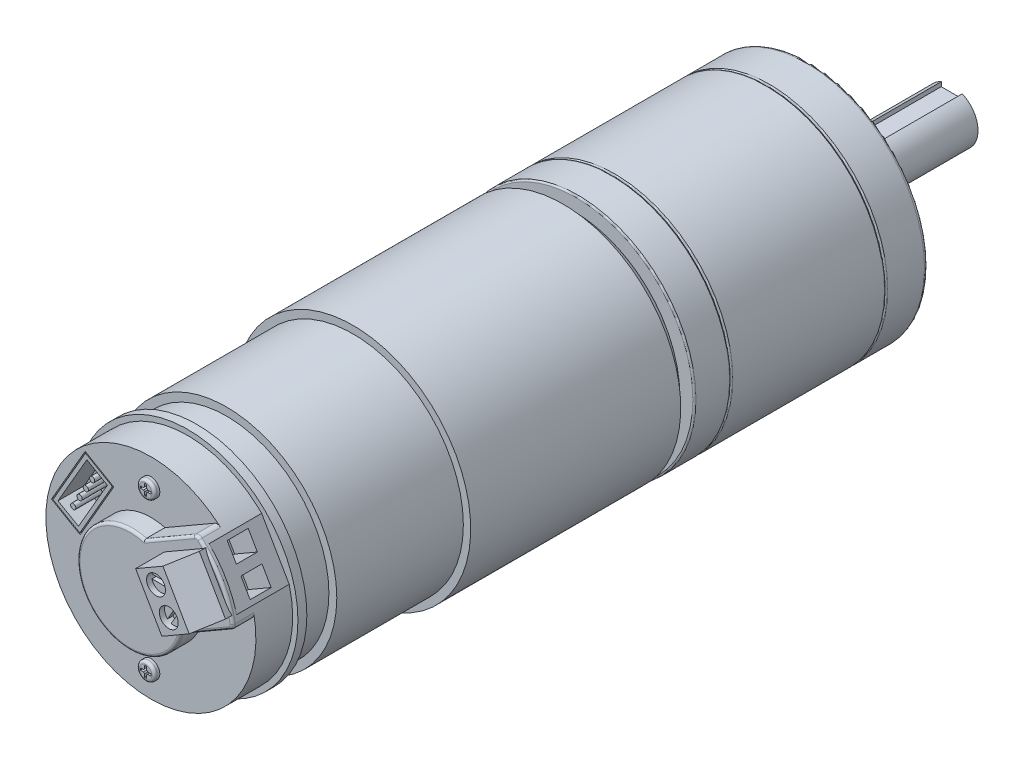
SolidWorks part; units mm, degrees
ref_plane "Front Plane" through (0, 0, 0) normal (0, 0, 1) x (1, 0, 0)
ref_plane "Top Plane" through (0, 0, 0) normal (0, 1, 0) x (1, 0, 0)
ref_plane "Right Plane" through (0, 0, 0) normal (1, 0, 0) x (0, 0, -1)
sketch "Sketch1" plane through (0, 0, 0) normal (0, 0, 1) x (1, 0, 0)
  circle A0 centre (-32.232, 14.9868) radius 22.5
extrude "Boss-Extrude1" add sketch "Sketch1" along normal blind 8
fillet "Fillet1" radius 0.3 1 edges at (-9.732, 14.9868, 8)
sketch "Sketch2" plane through (0, 0, 8) normal (0, 0, 1) x (1, 0, 0)
  circle A0 centre (-32.232, 14.9868) radius 22.5
extrude "Boss-Extrude2" add sketch "Sketch2" along normal blind 29.5
fillet "Fillet3" radius 0.3 1 edges at (-9.732, 14.9868, 37.5)
sketch "Sketch3" plane through (0, 0, 37.5) normal (0, 0, 1) x (1, 0, 0)
  circle A0 centre (-32.232, 14.9868) radius 22.5
extrude "Boss-Extrude5" add sketch "Sketch3" along normal blind 7
fillet "Fillet4" radius 0.3 3 edges at (-9.732, 14.9868, 8) (-9.732, 14.9868, 37.5) (-9.732, 14.9868, 44.5)
sketch "Sketch4" plane through (0, 0, 44.5) normal (0, 0, 1) x (1, 0, 0)
  circle A0 centre (-32.232, 14.9868) radius 5
extrude "Boss-Extrude7" add sketch "Sketch4" along normal blind 0.1
sketch "Sketch5" plane through (0, 0, 44.6) normal (0, 0, 1) x (1, 0, 0)
  circle A0 centre (-32.232, 14.9868) radius 21
extrude "Boss-Extrude8" add sketch "Sketch5" along normal blind 66.5
fillet "Fillet6" radius 2 1 edges at (-11.232, 14.9868, 44.6)
ref_plane "Plane1" through (0, 0, 47) normal (0, 0, 1) x (1, 0, 0)
sketch "Sketch6" plane through (0, 0, 47) normal (0, 0, 1) x (1, 0, 0)
  line L2 (-28.132, -5.609) -> (-28.132, -7.0347)
  line L4 (-36.332, -5.609) -> (-36.332, -7.0347)
  arc A0 (-28.132, -7.0347) -> (-36.332, -7.0347) centre (-32.232, 14.9868) ccw
  arc A1 (-28.132, -5.609) -> (-36.332, -5.609) centre (-32.232, 14.9868) ccw
  point P4 (-32.232, -6.0132)
extrude "Boss-Extrude9" add sketch "Sketch6" along normal blind 40
sketch "Sketch7" plane through (0, 0, 111.1) normal (0, 0, 1) x (1, 0, 0)
  circle A0 centre (-32.232, 14.9868) radius 19.5
extrude "Boss-Extrude10" add sketch "Sketch7" along normal blind 5.7
sketch "Sketch8" plane through (0, 0, 116.8) normal (0, 0, 1) x (1, 0, 0)
  circle A0 centre (-32.232, 14.9868) radius 21
extrude "Boss-Extrude11" add sketch "Sketch8" along normal blind 1.7
sketch "Sketch9" plane through (0, 0, 118.5) normal (0, 0, 1) x (1, 0, 0)
  circle A0 centre (-32.232, 14.9868) radius 20
extrude "Boss-Extrude12" add sketch "Sketch9" along normal blind 7
fillet "Fillet7" radius 0.7 1 edges at (-9.732, 14.9868, 0)
sketch "Sketch21" plane through (0, 0, 125.5) normal (0, 0, 1) x (1, 0, 0)
  line L0 (-45.6944, 15.3693) -> (-51.1503, 18.5193)
  line L2 (-39.2944, 26.4544) -> (-44.7503, 29.6044)
  line L3 (-44.7503, 29.6044) -> (-51.1503, 18.5193)
  line L4 (-39.2944, 26.4544) -> (-45.6944, 15.3693)
  point P6 (-42.4944, 20.9118)
extrude "Cut-Extrude5" cut sketch "Sketch21" against normal blind 5
sketch "Sketch22" plane through (0, 0, 120.5) normal (0, 0, 1) x (1, 0, 0)
  line L0 (-44.4209, 28.375) -> (-49.9209, 18.8487)
  line L1 (-49.9209, 18.8487) -> (-46.0238, 16.5987)
  line L2 (-46.0238, 16.5987) -> (-40.5238, 26.125)
  line L3 (-40.5238, 26.125) -> (-44.4209, 28.375)
  line L4 (-39.5676, 26.3812) -> (-44.6771, 29.3312)
  line L5 (-44.6771, 29.3312) -> (-50.8771, 18.5925)
  line L6 (-50.8771, 18.5925) -> (-45.7676, 15.6425)
  line L7 (-45.7676, 15.6425) -> (-39.5676, 26.3812)
  circle A0 centre (-45.8223, 21.4476) radius 0.5
  circle A1 centre (-47.0223, 19.3691) radius 0.5
  circle A2 centre (-43.4223, 25.6045) radius 0.5
  circle A3 centre (-44.6223, 23.5261) radius 0.5
extrude "Boss-Extrude20" add sketch "Sketch22" along normal blind 5 contours L6 L7 L4 L5 L3 L2 L1 L0 | A2 | A3 | A0 | A1 region at (-42.8213, 21.1006, 120.5) region at (-45.8223, 21.4476, 120.5) region at (-47.0223, 19.3691, 120.5) region at (-43.4223, 25.6045, 120.5) region at (-44.6223, 23.5261, 120.5)
sketch "Sketch23" plane through (0, 0, 125.5) normal (0, 0, 1) x (1, 0, 0)
  line L1 (-29.5473, 24.6197) -> (-20.1195, 30.0629)
  line L2 (-22.5473, 12.4954) -> (-13.1195, 17.9385)
  arc A0 (-29.5473, 24.6197) -> (-22.5473, 12.4954) centre (-32.232, 14.9868) ccw
  arc A1 (-13.1195, 17.9385) -> (-12.6399, 19.0055) centre (-13.6195, 18.8046) ccw
  arc A2 (-20.1195, 30.0629) -> (-18.9557, 29.9448) centre (-19.6195, 29.1969) cw
  arc A4 (-12.6399, 19.0055) -> (-18.9557, 29.9448) centre (-32.232, 14.9868) ccw
  point P10 (-42.4944, 20.9118)
  point P11 (-24.8334, 27.3413)
  dimension "D1" = 1
extrude "Boss-Extrude21" add sketch "Sketch23" along normal blind 4
sketch "Sketch24" plane through (0, 0, 129.5) normal (0, 0, 1) x (1, 0, 0)
  line L1 (-13.0177, 20.3067) -> (-20.6387, 15.9067)
  line L2 (-18.0177, 28.967) -> (-25.6387, 24.567)
  line L3 (-25.6387, 24.567) -> (-20.6387, 15.9067)
  line L4 (-18.0177, 28.967) -> (-13.0177, 20.3067)
  point P6 (-15.5177, 24.6368)
  point P7 (-23.1387, 20.2368)
extrude "Boss-Extrude22" add sketch "Sketch24" along normal blind 5.5
sketch "Sketch25" plane through (-12.0475, 20.8669, 0) normal (0.5, -0.866, 0) x (0.866, 0.5, 0)
  line L0 (-1.1203, 130.5) -> (-3.9203, 135)
  line L1 (-3.9203, 135) -> (-1.1203, 135)
  line L2 (-1.1203, 135) -> (-1.1203, 130.5)
extrude "Cut-Extrude6" cut sketch "Sketch25" against normal through all
sketch "Sketch26" plane through (0, 0, 125.5) normal (0, 0, 1) x (1, 0, 0)
  line L0 (-31.832, 29.7868) -> (-31.232, 29.7868)
  line L1 (-33.232, 29.7868) -> (-33.232, 30.1868)
  line L2 (-31.832, 30.1868) -> (-31.232, 30.1868)
  line L3 (-32.032, 30.3868) -> (-32.032, 30.9868)
  line L4 (-32.432, 30.3868) -> (-32.432, 30.9868)
  line L5 (-32.632, 30.1868) -> (-33.232, 30.1868)
  line L6 (-32.432, 30.9868) -> (-32.032, 30.9868)
  line L7 (-32.032, 29.5868) -> (-32.032, 28.9868)
  line L8 (-32.432, 29.5868) -> (-32.432, 28.9868)
  line L9 (-32.632, 29.7868) -> (-33.232, 29.7868)
  line L10 (-31.232, 30.1868) -> (-31.232, 29.7868)
  line L11 (-32.432, 28.9868) -> (-32.032, 28.9868)
  line L12 (-32.632, 29.7868) -> (-32.432, 29.5868)
  line L13 (-32.432, 30.3868) -> (-32.632, 30.1868)
  line L14 (-32.032, 30.3868) -> (-31.832, 30.1868)
  line L15 (-31.832, 29.7868) -> (-32.032, 29.5868)
  line L17 (-31.832, 0.1868) -> (-32.032, 0.3868)
  line L18 (-32.032, -0.4132) -> (-31.832, -0.2132)
  line L19 (-32.432, -0.4132) -> (-32.632, -0.2132)
  line L20 (-32.632, 0.1868) -> (-32.432, 0.3868)
  line L21 (-32.432, 0.9868) -> (-32.032, 0.9868)
  line L22 (-31.232, -0.2132) -> (-31.232, 0.1868)
  line L23 (-32.632, 0.1868) -> (-33.232, 0.1868)
  line L24 (-32.432, 0.3868) -> (-32.432, 0.9868)
  line L25 (-32.032, 0.3868) -> (-32.032, 0.9868)
  line L26 (-32.432, -1.0132) -> (-32.032, -1.0132)
  line L27 (-32.632, -0.2132) -> (-33.232, -0.2132)
  line L28 (-32.432, -0.4132) -> (-32.432, -1.0132)
  line L29 (-32.032, -0.4132) -> (-32.032, -1.0132)
  line L30 (-31.832, -0.2132) -> (-31.232, -0.2132)
  line L31 (-33.232, 0.1868) -> (-33.232, -0.2132)
  line L32 (-31.832, 0.1868) -> (-31.232, 0.1868)
  circle A0 centre (-32.232, 29.9868) radius 1.7
  circle A1 centre (-32.232, -0.0132) radius 1.7
  point P2 (-32.432, 29.7868)
  point P4 (-32.032, 30.1868)
  point P10 (-32.432, 30.1868)
  point P12 (-32.032, 29.7868)
  point P42 (-32.032, 0.1868)
  point P43 (-32.432, -0.2132)
  point P44 (-32.032, -0.2132)
  point P45 (-32.432, 0.1868)
  dimension "D1" = 0.2
  dimension "D2" = 0.2
  dimension "D3" = 0.2
  dimension "D4" = 0.2
  dimension "D5" = 0.2
  dimension "D6" = 0.2
  dimension "D7" = 0.2
  dimension "D8" = 0.2
extrude "Boss-Extrude23" add sketch "Sketch26" along normal blind 1
fillet "Fillet9" radius 0.5 2 edges at (-33.932, -0.0132, 126.5) (-30.532, 29.9868, 126.5)
sketch "Sketch27" plane through (0, 0, 135) normal (0, 0, 1) x (1, 0, 0)
  circle A0 centre (-21.7546, 23.8395) radius 1.8
  circle A1 centre (-19.3267, 19.6342) radius 1.8
extrude "Cut-Extrude7" cut sketch "Sketch27" against normal blind 1
sketch "Sketch29" plane through (0, 0, 134) normal (0, 0, 1) x (1, 0, 0)
  line L1 (-23.5096, 23.4395) -> (-19.9996, 23.4395)
  line L3 (-23.5096, 24.2395) -> (-19.9996, 24.2395)
  line L7 (-19.8577, 17.9143) -> (-18.1028, 20.9541)
  line L8 (-20.5506, 18.3143) -> (-18.7956, 21.3541)
  arc A0 (-23.5096, 24.2395) -> (-23.5096, 23.4395) centre (-21.7546, 23.8395) ccw
  arc A1 (-19.9996, 23.4395) -> (-19.9996, 24.2395) centre (-21.7546, 23.8395) ccw
  arc A2 (-18.6805, 21.3142) -> (-18.1028, 20.9541) centre (-19.3267, 19.6342) cw
  arc A3 (-19.8577, 17.9143) -> (-20.5506, 18.3143) centre (-19.3267, 19.6342) cw
  arc A4 (-18.7956, 21.3541) -> (-18.1028, 20.9541) centre (-19.3267, 19.6342) cw
  circle M1 centre (-21.7546, 23.8395) radius 1.8
extrude "Cut-Extrude8" cut sketch "Sketch29" against normal blind 1 contours L3 L1 M1 | A4 L8 A3 L7 A2 region at (-21.7546, 23.8395, 134) region at (-19.3267, 19.6342, 134)
sketch "Sketch30" plane through (-0.9702, -0.5601, 0) normal (0.866, 0.5, 0) x (0, 0, -1)
  line L5 (-118.5, 23.595) -> (-128.5, 23.595)
  line L6 (-118.5, 23.595) -> (-118.5, 34.595)
  line L7 (-118.5, 34.595) -> (-128.5, 34.595)
  line L8 (-128.5, 23.595) -> (-128.5, 34.595)
  point P4 (-123.5, 29.095)
extrude "Cut-Extrude9" cut sketch "Sketch30" along normal blind 1
sketch "Sketch31" plane through (-0.9702, -0.5601, 0) normal (0.866, 0.5, 0) x (0, 0, -1)
  line L6 (-125.5, 28.2225) -> (-121.5, 28.2225)
  line L7 (-125.5, 29.9675) -> (-121.5, 29.9675)
  line L8 (-125.5, 29.9675) -> (-125.5, 33.4675)
  line L9 (-125.5, 33.4675) -> (-121.5, 33.4675)
  line L10 (-121.5, 29.9675) -> (-121.5, 33.4675)
  line L13 (-121.5, 28.2225) -> (-121.5, 24.7225)
  line L14 (-125.5, 24.7225) -> (-121.5, 24.7225)
  line L15 (-125.5, 28.2225) -> (-125.5, 24.7225)
  point P9 (-123.5, 31.7175)
extrude "Cut-Extrude10" cut sketch "Sketch31" against normal blind 5
fillet "Fillet10" radius 0.5 6 edges at (-17.8334, 15.217, 129.5) (-12.7074, 18.3946, 129.5) (-14.9115, 24.9868, 129.5) (-19.5185, 30.1918, 129.5) (-24.8334, 27.3413, 129.5) (-40.8922, 9.9868, 129.5)
sketch "Sketch32" plane through (0, 0, 0) normal (0, 0, -1) x (-1, 0, 0)
  circle A0 centre (32.232, 14.9868) radius 13
extrude "Boss-Extrude24" add sketch "Sketch32" along normal blind 1.5
sketch "Sketch33" plane through (0, 0, 0) normal (0, 0, -1) x (-1, 0, 0)
  circle A1 centre (32.232, 32.7368) radius 3.85
  circle A2 centre (49.982, 14.9868) radius 3.85
  circle A3 centre (32.232, -2.7632) radius 3.85
  circle A4 centre (14.482, 14.9868) radius 3.85
  point P14 (32.232, 14.9868)
  dimension "D1" = 4
extrude "Cut-Extrude11" cut sketch "Sketch33" against normal blind 3
sketch "Sketch34" plane through (0, 0, 3) normal (0, 0, -1) x (-1, 0, 0)
  line L1 (32.232, 35.0462) -> (30.232, 33.8915)
  line L2 (30.232, 33.8915) -> (30.232, 31.5821)
  line L3 (30.232, 31.5821) -> (32.232, 30.4274)
  line L4 (32.232, 30.4274) -> (34.232, 31.5821)
  line L5 (34.232, 31.5821) -> (34.232, 33.8915)
  line L6 (34.232, 33.8915) -> (32.232, 35.0462)
  line L7 (52.2914, 14.9868) -> (51.1367, 16.9868)
  line L8 (51.1367, 12.9868) -> (52.2914, 14.9868)
  line L9 (48.8273, 12.9868) -> (51.1367, 12.9868)
  line L10 (47.6726, 14.9868) -> (48.8273, 12.9868)
  line L11 (48.8273, 16.9868) -> (47.6726, 14.9868)
  line L12 (51.1367, 16.9868) -> (48.8273, 16.9868)
  line L13 (32.232, -5.0726) -> (34.232, -3.9179)
  line L14 (30.232, -3.9179) -> (32.232, -5.0726)
  line L15 (30.232, -1.6085) -> (30.232, -3.9179)
  line L16 (32.232, -0.4538) -> (30.232, -1.6085)
  line L17 (34.232, -1.6085) -> (32.232, -0.4538)
  line L18 (34.232, -3.9179) -> (34.232, -1.6085)
  line L19 (12.1726, 14.9868) -> (13.3273, 12.9868)
  line L20 (13.3273, 16.9868) -> (12.1726, 14.9868)
  line L21 (15.6367, 16.9868) -> (13.3273, 16.9868)
  line L22 (16.7914, 14.9868) -> (15.6367, 16.9868)
  line L23 (15.6367, 12.9868) -> (16.7914, 14.9868)
  line L24 (13.3273, 12.9868) -> (15.6367, 12.9868)
  circle A0 centre (32.232, 32.7368) radius 3
  circle A1 centre (32.232, 32.7368) radius 2 construction
  circle A2 centre (49.982, 14.9868) radius 3
  circle A3 centre (32.232, -2.7632) radius 3
  circle A4 centre (14.482, 14.9868) radius 3
  point P40 (32.232, 14.9868)
  dimension "D1" = 4
extrude "Boss-Extrude25" add sketch "Sketch34" along normal blind 3
fillet "Fillet11" radius 0.5 24 edges at (-30.232, -2.7632, 3) (-31.232, -1.0311, 3) (-33.232, -1.0311, 3) (-34.232, -2.7632, 3) (-33.232, -4.4952, 3) (-31.232, -4.4952, 3) (-49.982, 12.9868, 3) (-48.2499, 13.9868, 3) (-48.2499, 15.9868, 3) (-49.982, 16.9868, 3) (-51.714, 15.9868, 3) (-51.714, 13.9868, 3) (-14.482, 16.9868, 3) (-16.214, 15.9868, 3) (-16.214, 13.9868, 3) (-14.482, 12.9868, 3) (-12.7499, 13.9868, 3) (-12.7499, 15.9868, 3) (-34.232, 32.7368, 3) (-33.232, 31.0048, 3) (-31.232, 31.0048, 3) (-30.232, 32.7368, 3) (-31.232, 34.4689, 3) (-33.232, 34.4689, 3)
sketch "Sketch35" plane through (0, 0, 0) normal (0, 0, -1) x (-1, 0, 0)
  circle A2 centre (44.7831, 27.538) radius 2
  circle A4 centre (44.7831, 2.4357) radius 2
  circle A6 centre (19.6808, 2.4357) radius 2
  circle A8 centre (19.6808, 27.538) radius 2
  point P22 (32.232, 14.9868)
extrude "Cut-Extrude12" cut sketch "Sketch35" against normal blind 5
sketch "Sketch36" plane through (0, 0, -1.5) normal (0, 0, -1) x (-1, 0, 0)
  circle A0 centre (32.232, 14.9868) radius 5
extrude "Boss-Extrude26" add sketch "Sketch36" along normal blind 25.5
sketch "Sketch37" plane through (0, 0, -27) normal (0, 0, -1) x (-1, 0, 0)
  line L1 (30.232, 21.2368) -> (34.232, 21.2368)
  line L2 (30.232, 21.2368) -> (30.232, 18.7368)
  line L3 (30.232, 18.7368) -> (34.232, 18.7368)
  line L4 (34.232, 21.2368) -> (34.232, 18.7368)
  line L5 (30.232, 21.2368) -> (34.232, 18.7368) construction
  line L6 (30.232, 18.7368) -> (34.232, 21.2368) construction
  circle A0 centre (32.232, 14.9868) radius 5 construction
  circle A1 centre (32.232, 14.9868) radius 5 construction
  point P0 (32.232, 19.9868)
extrude "Cut-Extrude13" cut sketch "Sketch37" against normal blind 20
fillet "Fillet12" radius 2 2 edges at (-30.232, 19.1531, -7) (-34.232, 19.1531, -7)
